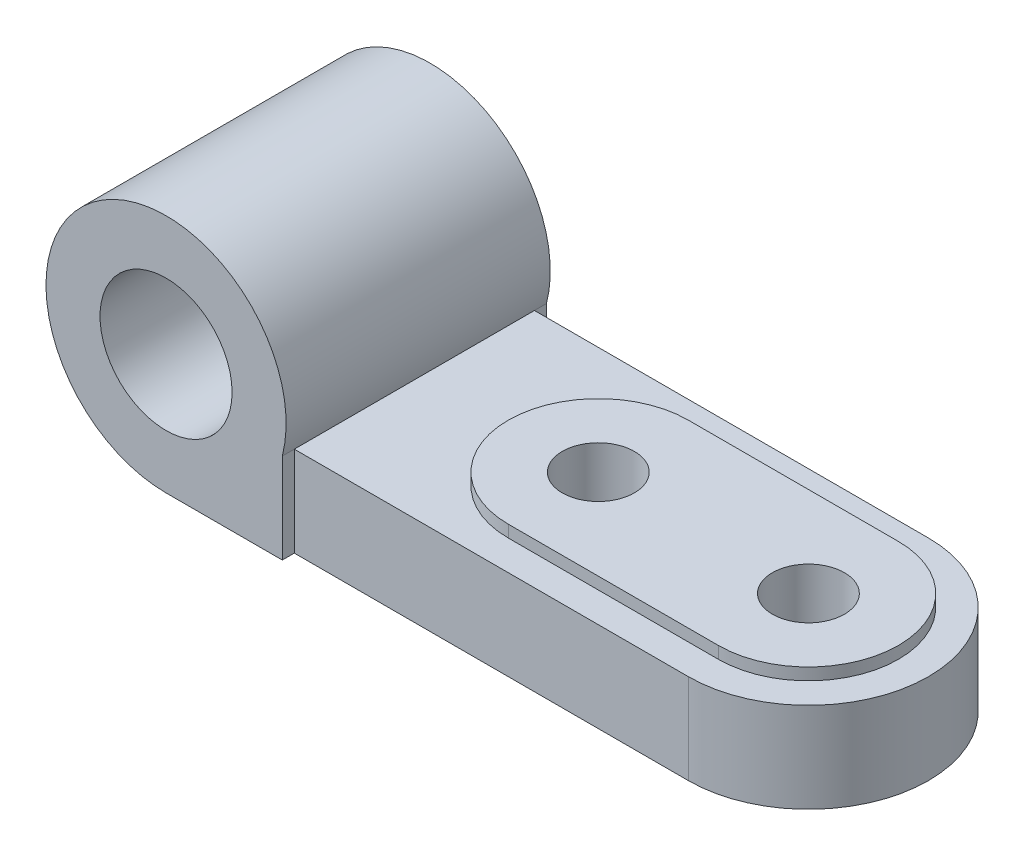
SolidWorks part; units mm, degrees
ref_plane "Front" through (0, 0, 0) normal (0, 0, 1) x (1, 0, 0)
ref_plane "Top" through (0, 0, 0) normal (0, 1, 0) x (1, 0, 0)
ref_plane "Right" through (0, 0, 0) normal (1, 0, 0) x (0, 0, -1)
sketch "Sketch1" plane through (0, 0, 0) normal (0, 0, 1) x (1, 0, 0)
  line L0 (-57.8091, -20) -> (47.1909, -20)
  line L1 (47.1909, -20) -> (47.1909, -5)
  line L2 (47.1909, -5) -> (-38.4442, -5)
  circle A0 centre (-57.8091, 0) radius 20
  circle A1 centre (-57.8091, 0) radius 11
extrude "Boss-Extrude1" add sketch "Sketch1" along normal blind 44 contours A0 A1 region at (-71.5513, 13.7421, 0)
extrude "Boss-Extrude2" add sketch "Sketch1<5>" along normal blind 44 contours A0 L0 L1 L2 region at (1.7589, -12.6982, 0)
sketch "Sketch1<5>" plane through (0, 0, 0) normal (0, 0, 1) x (1, 0, 0) same geometry as "Sketch1"
sketch "Sketch2" plane through (0, -5, 0) normal (0, 1, 0) x (1, 0, 0)
  line L0 (-38.4442, 0) -> (-38.4442, -2)
  line L1 (-38.4442, -44) -> (-38.4442, 0) construction
  line L2 (-38.4442, -2) -> (47.1909, -2)
  line L3 (47.1909, -44) -> (47.1909, 0) construction
  line L4 (47.1909, -2) -> (47.1909, -42)
  line L5 (47.1909, -42) -> (-38.4442, -42)
  line L6 (-38.4442, -42) -> (-38.4442, -2)
  circle A0 centre (27.1909, -22) radius 20
  line M5 (47.1909, 0) -> (-38.4442, 0)
  line M6 (-38.4442, 0) -> (-38.4442, -44)
  line M7 (-38.4442, -44) -> (47.1909, -44)
  line M8 (47.1909, -44) -> (47.1909, 0)
extrude "Cut-Extrude1" cut sketch "Sketch2" against normal blind 44 contours A0 L5 M8 | A0 L4 L2 | L5 M8 M6 M7 | L2 M6 M8 M5 region at (4.3733, -5, 1) region at (42.7235, -5, 6.4674) region at (4.3733, -5, 43) region at (42.7235, -5, 37.5326)
sketch "Sketch3" plane through (0, -5, 0) normal (0, 1, 0) x (1, 0, 0)
  line L0 (27.1909, -22) -> (-38.4442, -22)
  line L1 (-38.4442, -42) -> (-38.4442, -2) construction
  line L2 (27.1909, -22) -> (-7.8091, -22)
  line L3 (-7.8091, -37) -> (27.1909, -37)
  line L4 (-7.8091, -7) -> (27.1909, -7)
  circle A0 centre (27.1909, -22) radius 15
  circle A1 centre (-7.8091, -22) radius 15
extrude "Boss-Extrude3" add sketch "Sketch3" along normal blind 2 contours A1 L0 | L0 A1 | A1 L2 A0 L4 | A1 L3 A0 L2 | A0 region at (-7.8091, -5, 28.3662) region at (9.6909, -5, 12.1644) region at (-7.8091, -5, 15.6338) region at (9.6909, -5, 31.8356) region at (16.8843, -5, 11.6934)
sketch "Sketch4" plane through (0, -3, 0) normal (0, 1, 0) x (1, 0, 0)
  circle A0 centre (27.1909, -22) radius 6
  circle A1 centre (-7.8091, -22) radius 6
extrude "Cut-Extrude2" cut sketch "Sketch4" against normal blind 44 contours A0 | A1
